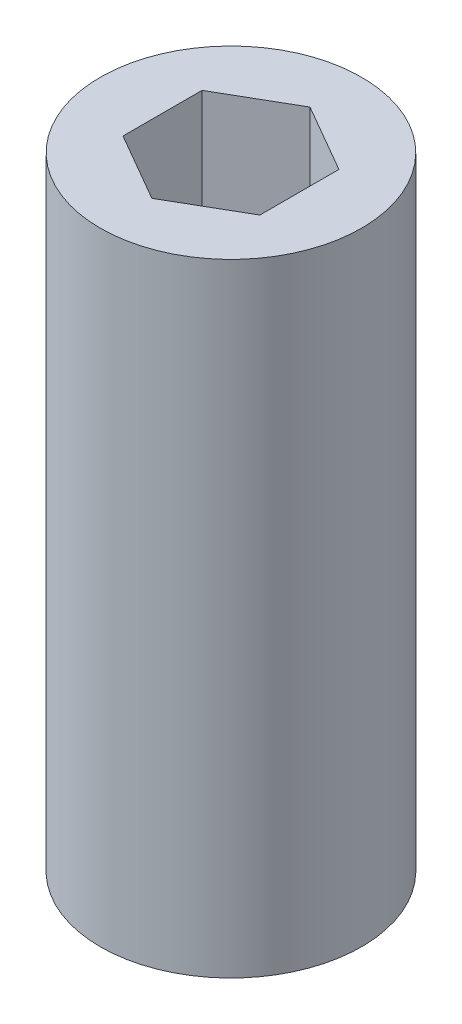
SolidWorks part; units mm, degrees
material "6061-T6 (SS)"
ref_plane "Front Plane" through (0, 0, 0) normal (0, 0, 1) x (1, 0, 0)
ref_plane "Top Plane" through (0, 0, 0) normal (0, 1, 0) x (1, 0, 0)
ref_plane "Right Plane" through (0, 0, 0) normal (1, 0, 0) x (0, 0, -1)
ref_axis "Axis1" through (0, 0, 55) along (0, 0, -1)
sketch "Sketch1" plane through (0, 0, 0) normal (0, 1, 0) x (1, 0, 0)
  line L1 (1.1, -0.6351) -> (1.1, 0.6351)
  line L2 (1.1, 0.6351) -> (0, 1.2702)
  line L3 (0, 1.2702) -> (-1.1, 0.6351)
  line L4 (-1.1, 0.6351) -> (-1.1, -0.6351)
  line L5 (-1.1, -0.6351) -> (0, -1.2702)
  line L6 (0, -1.2702) -> (1.1, -0.6351)
  circle A0 centre (0, 0) radius 1.1 construction
  circle A1 centre (0, 0) radius 2.1
  dimension "D1" = 2.2
  dimension "D2" = 1
extrude "Boss-Extrude1" add sketch "Sketch1" along normal blind 10
